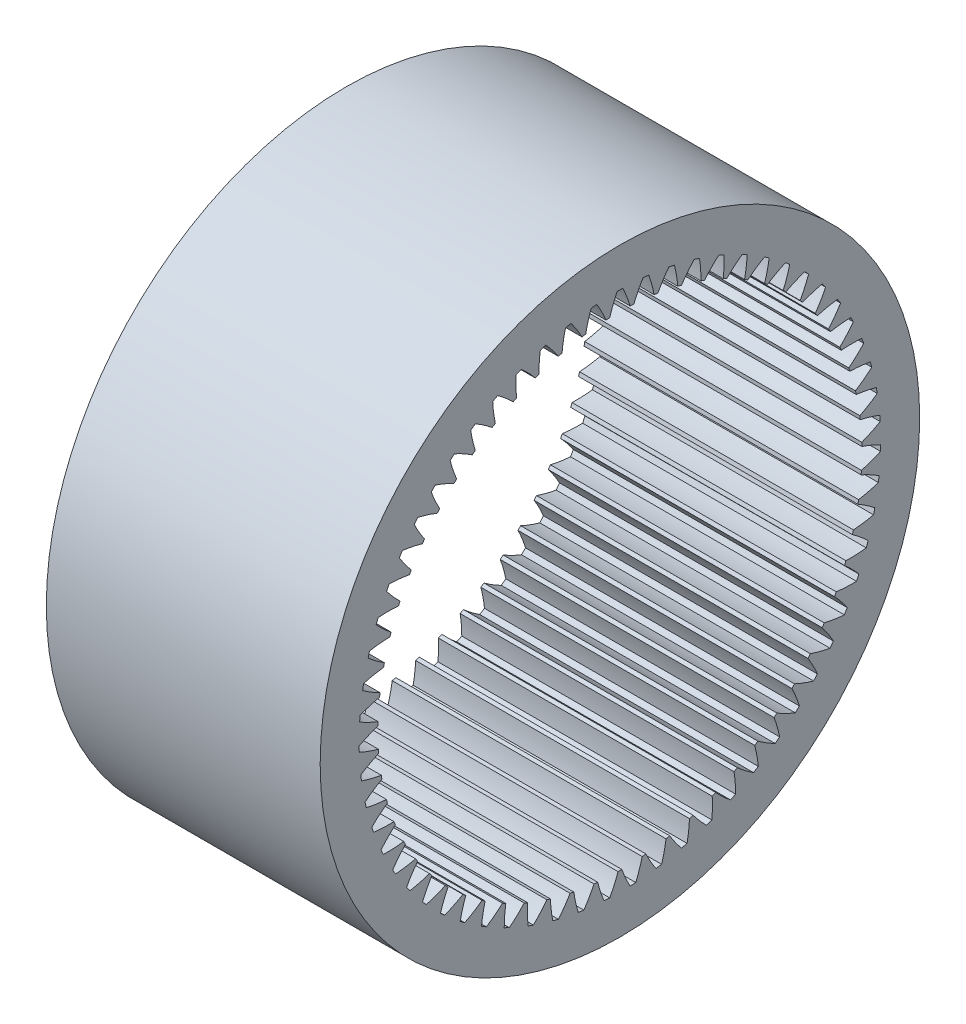
SolidWorks part; units mm, degrees
ref_plane "Plane1" through (0, 0, 0) normal (0, 0, 1) x (1, 0, 0)
ref_plane "Plane2" through (0, 0, 0) normal (0, 1, 0) x (1, 0, 0)
ref_plane "Plane3" through (0, 0, 0) normal (1, 0, 0) x (0, 0, -1)
sketch "HoldingSke" plane through (0, 0, 0) normal (0, 1, 0) x (1, 0, 0)
  line L0 (0, 0) -> (0.5, -0.866)
  line L1 (-15, 0) -> (100, 0) construction
  line L2 (0, 0) -> (-2.1039, 2.3779)
  line L3 (0, 0) -> (-11.863, 4.5341)
  line L4 (0, 0) -> (4.318, 7.479)
  line L5 (0, 0) -> (-23.7986, -8.8762)
  line L6 (0, 0) -> (-10.5278, -7.1032)
  line L7 (-2.1039, 2.3779) -> (3.3635, 27.1825)
  line L8 (-76.2, 3.3779) -> (-54.61, 3.3779)
  line L9 (-71.009, 38.7566) -> (-53.1078, 45.2721)
  line L10 (-76.2, 71.12) -> (104.1128, 71.12)
  line L11 (0, 0) -> (-12, 0)
  line L12 (-76.2, 101.6) -> (-76.162, 101.6)
  line L13 (24.9733, 27.94) -> (52.9518, 28.4284)
  line L14 (24.9733, 27.94) -> (24.9743, 27.94)
  line L15 (24.9733, 27.94) -> (100.4006, 29.5858)
  circle A0 centre (0, 0) radius 12.5
  circle A1 centre (0, 0) radius 12.7
  circle A2 centre (0, 0) radius 12.7
  dimension "MHD" = 25.4
  dimension "Hub_dia" = 25.4
  dimension "Diameter" = 25
  dimension "Num_teeth" = 60
  dimension "Pitch" = 1
  dimension "Overall_len" = 25.4
  dimension "Show_teeth" = 60
  dimension "Thickness" = 12.7
  dimension "OAL" = 25.4001
  dimension "T_dim" = 21.59
  dimension "Ap" = 20
  dimension "H" = 19.05
  dimension "Pitch_radius" = 180.3128
  dimension "Width" = 12
  dimension "Backlash" = 0.038
  dimension "Addendum_fac" = 1
  dimension "Dedendum_fac" = 1.25
  dimension "Clearance_fac" = 0.25
  dimension "Dedendum_add" = 0.001
  dimension "Module" = 1
sketch "BasProSke" plane through (0, 0, 0) normal (0, 1, 0) x (1, 0, 0)
  line L0 (-10, 0) -> (60, 0) construction
  line L1 (0, 29) -> (0, 31.2764)
  line L2 (0, 29) -> (32.815, 29)
  line L3 (32.815, 29) -> (32.815, 31.2764)
  line L4 (32.815, 31.2764) -> (0, 31.2764)
  dimension "Thickness" = 32.815
  dimension "Diameter" = 62.5528
  dimension "Inside_diameter" = 58
revolve "Base-Revolve" add sketch "BasProSke" angle 360 about L0
sketch "TooCutSke" plane through (0, 0, 0) normal (1, 0, 0) x (0, 0, -1)
  line L3 (0.8803, 29.9871) -> (0.8803, 53.6633) construction
  line L4 (0, 0) -> (0, 59.563) construction
  line L5 (0, 0) -> (-3.576, 68.2339) construction
  line L6 (-13.1633, 24.7167) -> (36.4631, 27.3175) construction
  circle A0 centre (0, 0) radius 30 construction
  circle A1 centre (0, 0) radius 31.251 construction
  circle A2 centre (0, 0) radius 25.3717 construction
  circle A3 centre (0, 0) radius 28.9746 construction
  arc A4 (1.2274, 28.9486) -> (0.3395, 31.2492) centre (-13.1633, 24.7167) ccw
  arc A5 (1.2274, 28.9486) -> (-1.2274, 28.9486) centre (0, 0) ccw
  arc A6 (0.3395, 31.2492) -> (-0.3395, 31.2492) centre (0, 0) ccw
  arc A7 (-0.3395, 31.2492) -> (-1.2274, 28.9486) centre (13.1633, 24.7167) ccw
  dimension "Pitch_dia" = 60
  dimension "Base_dia" = 50.7434
  dimension "Root_dia" = 62.502
  dimension "Overcut_dia" = 57.9492
  dimension "Flank_rad" = 15
  dimension "Half_ang" = 3
  dimension "Half_CT" = 0.8803
extrude "ToothCut" cut sketch "TooCutSke" along normal through all
fillet "Breaks" [suppressed] radius 0.1
fillet "RootFillets" [suppressed] radius 0.251
pattern_circular "TeethCuts" count 63 over 360 about axis through (-10, 0, 0) along (1, 0, 0) of "ToothCut"
scale "Scale1" scale about centroid uniform scaling yes scale factor 2
sketch "Sketch1" plane through (49.2225, 0, 0) normal (1, 0, 0) x (0, 0, -1)
  circle A0 centre (0, 0) radius 62.5528
sketch "Sketch2" plane through (49.2225, 0, 0) normal (1, 0, 0) x (0, 0, -1)
  circle A0 centre (0, 0) radius 72.5528
  circle A1 centre (0, 0) radius 62.5528
extrude "Boss-Extrude1" add sketch "Sketch2" against normal blind 65.63
scale "Scale2" scale about centroid uniform scaling yes scale factor 1.1
scale "Scale3" scale about centroid uniform scaling yes scale factor 1.01
scale "Scale4" scale about centroid uniform scaling yes scale factor 0.990099
scale "Scale5" scale about centroid uniform scaling yes scale factor 0.909091
scale "Scale6" scale about centroid uniform scaling yes scale factor 1.01
sketch "Sketch3" plane through (-16.7356, 0, 0) normal (-1, 0, 0) x (0, 0, 1)
  circle A0 centre (0, 0) radius 72.5528
  circle A1 centre (0, 0) radius 73.2783
extrude "Cut-Extrude1" cut sketch "Sketch3" against normal through all
equation "' \"Module@HoldingSke\" = 6.35"
equation "' \"Num_teeth@HoldingSke\" = 24"
equation "' \"Ap@HoldingSke\" =  14.5"
equation "' \"Ap@HoldingSke\" = 14.5"
equation "' \"Width@HoldingSke\" = 12"
equation "' \"Diameter@HoldingSke\" = 8 * 25.4"
equation "' \"Show_teeth@HoldingSke\" = 100"
equation "' \"Backlash@HoldingSke\" = 0.009 * 25.4"
equation "' \"Addendum_fac@HoldingSke\" = 1.0"
equation "' \"Dedendum_fac@HoldingSke\" = 1.25"
equation "' \"Dedendum_add@HoldingSke\" = 0.00005 * 25.4"
equation "' \"Clearance_fac@HoldingSke\" = 0.25"
equation "\"Pitch@HoldingSke\" = 1 / \"Module@HoldingSke\" "
equation "\"Overcut_dia@TooCutSke\" = (\"Num_teeth@HoldingSke\" - 2 * \"Addendum_fac@HoldingSke\") / \"Pitch@HoldingSke\" - 0.002 * 25.4"
equation "\"Pitch_dia@TooCutSke\" = \"Num_teeth@HoldingSke\" / \"Pitch@HoldingSke\""
equation "\"Base_dia@TooCutSke\" = \"Num_teeth@HoldingSke\" / \"Pitch@HoldingSke\" * cos((\"Ap@HoldingSke\"  * 3.14159265 / 180)) * 0.90"
equation "\"Root_dia@TooCutSke\" = \"Num_teeth@HoldingSke\"  / \"Pitch@HoldingSke\" + 2 *  \"Dedendum_fac@HoldingSke\"/ \"Pitch@HoldingSke\" + \"Dedendum_add@HoldingSke\" * 2"
equation "\"Half_ang@TooCutSke\" = 180 / \"Num_teeth@HoldingSke\""
equation "\"Half_CT@TooCutSke\" = \"Num_teeth@HoldingSke\" / \"Pitch@HoldingSke\" * sin((3.14159265 / 2 / \"Num_teeth@HoldingSke\")) / 2 + 10 * \"Backlash@HoldingSke\" / 4"
equation "\"Flank_rad@TooCutSke\" = \"Num_teeth@HoldingSke\" / \"Pitch@HoldingSke\" / 4"
equation "\"Radius@RootFillets\"= \"Clearance_fac@HoldingSke\" / \"Pitch@HoldingSke\" + \"Dedendum_add@HoldingSke\""
equation "\"Break_rad@Breaks\" = 0.02 / \"Pitch@HoldingSke\" * 5"
equation "\"Diameter@BasProSke\" = \"Num_teeth@HoldingSke\"  / \"Pitch@HoldingSke\" + 2 *  \"Dedendum_fac@HoldingSke\"/ \"Pitch@HoldingSke\" + \"Dedendum_add@HoldingSke\" * 2 + 0.002 * 25.4"
equation "\"Diameter@BasProSke\" = ((sgn( \"Diameter@BasProSke\"  - \"Diameter@HoldingSke\" )+1)*( \"Diameter@BasProSke\"  - \"Diameter@HoldingSke\" ))/2 + \"Diameter@HoldingSke\""
equation "\"Inside_diameter@BasProSke\" =  (\"Num_teeth@HoldingSke\" - 2 * \"Addendum_fac@HoldingSke\") / \"Pitch@HoldingSke\" "
